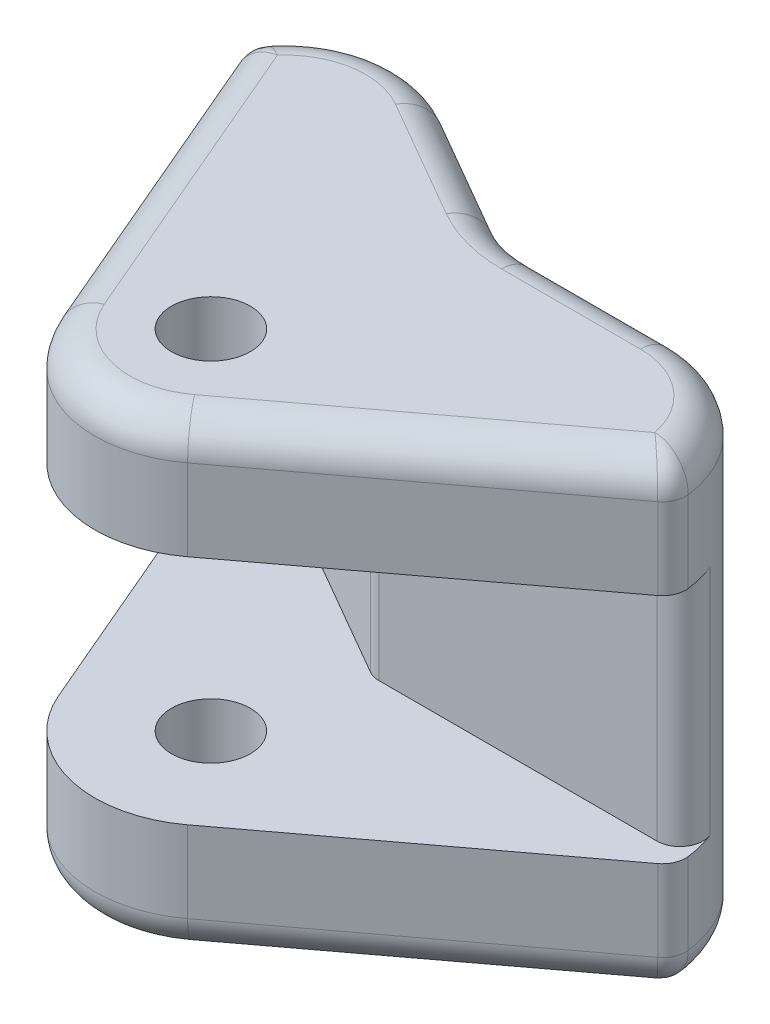
SolidWorks part; units mm, degrees
ref_plane "Front Plane" through (0, 0, 0) normal (0, 0, 1) x (1, 0, 0)
ref_plane "Top Plane" through (0, 0, 0) normal (0, 1, 0) x (1, 0, 0)
ref_plane "Right Plane" through (0, 0, 0) normal (1, 0, 0) x (0, 0, -1)
sketch "Sketch1" plane through (0, 0, 0) normal (0, 1, 0) x (1, 0, 0)
  line L0 (0, 0) -> (10, 0) construction
  line L6 (0, -5) -> (10, -5)
  line L7 (0, 0) -> (-8.6603, 5) construction
  line L8 (-2.5, -4.3301) -> (-11.1603, 0.6699)
  line L10 (-12.9904, 7.5) -> (-10.4904, 11.8301)
  line L11 (15, 0) -> (15, 5)
  line L12 (-3.6603, 13.6603) -> (1.5192, 10.6699)
  line L13 (4.0192, 10) -> (10, 10)
  line L14 (0, 0) -> (0, -5) construction
  line L15 (0, 0) -> (-2.5, -4.3301) construction
  arc A8 (10, -5) -> (15, 0) centre (10, 0) ccw
  arc A10 (-12.9904, 7.5) -> (-11.1603, 0.6699) centre (-8.6603, 5) ccw
  arc A11 (1.5192, 10.6699) -> (4.0192, 10) centre (4.0192, 15) ccw
  arc A12 (-10.4904, 11.8301) -> (-3.6603, 13.6603) centre (-6.1603, 9.3301) cw
  arc A13 (15, 5) -> (10, 10) centre (10, 5) ccw
  arc A14 (-2.5, -4.3301) -> (0, -5) centre (0, 0) ccw
  circle A15 centre (0, 0) radius 1.7
  point P3 (5, 0)
  point P8 (-4.3301, 2.5)
  point P25 (-7.9904, 16.1603)
  point P28 (15, 10)
  dimension "D1" = 5.9808
  dimension "D2" = 5
  dimension "D3" = 150
  dimension "D4" = 10
  dimension "D9" = 5
  dimension "D10" = 5
  dimension "D11" = 5
  dimension "D15" = 3.4
  dimension "D5" = 10
  dimension "D6" = 10
  dimension "D7" = 10
  dimension "D8" = 150
  dimension "D12" = 5
  dimension "D13" = 8.6603
  dimension "D14" = 150
extrude "Boss-Extrude1" add sketch "Sketch1" along normal blind 5
sketch "Sketch2" plane through (0, 5, 0) normal (0, 1, 0) x (1, 0, 0)
  line L0 (0, 0) -> (-8.6603, 5) construction
  line L2 (1.3397, 5) -> (-6.1603, 9.3301)
  line L3 (0, 0) -> (10, 0) construction
  line L4 (1.3397, 5) -> (10, 5)
  line L7 (-3.6603, 13.6603) -> (1.5192, 10.6699)
  line L8 (4.0192, 10) -> (10, 10)
  line L11 (10, 10) -> (4.0192, 10) construction
  line L13 (1.5192, 10.6699) -> (-3.6603, 13.6603) construction
  line L14 (10, 5) -> (15, 5)
  line L15 (-6.1603, 9.3301) -> (-10.4904, 11.8301)
  arc A0 (1.5192, 10.6699) -> (4.0192, 10) centre (4.0192, 15) ccw
  arc A1 (-3.6603, 13.6603) -> (-10.4904, 11.8301) centre (-6.1603, 9.3301) ccw
  arc A2 (15, 5) -> (10, 10) centre (10, 5) ccw
  point P4 (-4.3301, 2.5)
  point P9 (5, 0)
  dimension "D4" = 5
  dimension "D5" = 5
  dimension "D1" = 150
  dimension "D2" = 11.8301
  dimension "D3" = 6.8301
extrude "Boss-Extrude2" add sketch "Sketch2" along normal blind 10
sketch "Sketch3" plane through (0, 15, 0) normal (0, 1, 0) x (1, 0, 0)
  line L0 (-10.4904, 11.8301) -> (-4.5981, -1.9641)
  line L1 (15, 5) -> (3, -4)
  line L2 (10, 10) -> (4.0192, 10)
  line L3 (1.5192, 10.6699) -> (-3.6603, 13.6603)
  line L4 (1.5192, 10.6699) -> (-3.6603, 13.6603) construction
  arc A0 (-4.5981, -1.9641) -> (3, -4) centre (0, 0) ccw
  arc A1 (-2.5, -4.3301) -> (0, -5) centre (0, 0) ccw construction
  arc A2 (4.0192, 10) -> (1.5192, 10.6699) centre (4.0192, 15) cw
  arc A3 (-10.4904, 11.8301) -> (-3.6603, 13.6603) centre (-6.1603, 9.3301) cw
  arc A4 (10, 10) -> (15, 5) centre (10, 5) cw
  arc A5 (15, 5) -> (10, 10) centre (10, 5) ccw construction
  arc A6 (-3.6603, 13.6603) -> (-10.4904, 11.8301) centre (-6.1603, 9.3301) ccw construction
  circle A7 centre (0, 0) radius 1.7
  dimension "D1" = 5
  dimension "D2" = 3.4
extrude "Boss-Extrude3" add sketch "Sketch3" along normal blind 5
sketch "Sketch4" plane through (0, 5, 0) normal (0, 1, 0) x (1, 0, 0)
  line L0 (-10.4904, 11.8301) -> (1.3397, 5)
  line L1 (1.3397, 5) -> (15, 5)
  line L2 (1.3397, 5) -> (15, 5) construction
  line L3 (-10.4904, 11.8301) -> (1.3397, 5) construction
  line L4 (-10.4904, 11.8301) -> (-10.2404, 12.2631)
  line L5 (-10.2404, 12.2631) -> (1.4737, 5.5)
  line L6 (1.4737, 5.5) -> (15, 5.5)
  line L7 (15, 5.5) -> (15, 5)
  point P11 (3.2079, 12.0935)
  dimension "D1" = 0.5
  dimension "D2" = 0.5
extrude "Cut-Extrude1" cut sketch "Sketch4" along normal blind 10
fillet "Fillet1" radius 1 3 edges at (1.4737, 10, -5.5) (-10.2187, 10, -12.2506) (14.9749, 10, -5.5)
fillet "Fillet2" radius 1 2 edges at (-10.4904, 17.5, -11.8301) (15, 17.5, -5)
fillet "Fillet3" radius 1.5 22 edges at (-13.4899, 0, -3.7059) (-11.7404, 0, -9.6651) (-7.4543, 0, -14.1598) (-1.0705, 0, -12.1651) (2.7251, 0, -10.1704) (7.0096, 0, -10) (13.5355, 0, -8.5355) (15, 0, -2.5) (13.5355, 0, 3.5355) (5, 0, 5) (-1.2941, 0, 4.8296) (-10.3531, 20, -11.8497) (-7.1627, 20, -14.2286) (-1.0705, 20, -12.1651) (2.7251, 20, -10.1704) (7.0096, 20, -10) (13.3173, 20, -8.741) (14.8909, 20, -5.0856) (8.7856, 20, -0.3392) (-1.2941, 20, 4.8296) (-6.8301, 0, 1.8301) (-7.439, 20, -4.6866)
sketch "Sketch5" plane through (0, 0, 0) normal (0, -1, 0) x (1, 0, 0)
  line L1 (-0.8368, 3.123) -> (-3.123, 0.8368)
  line L2 (-3.123, 0.8368) -> (-2.2862, -2.2862)
  line L3 (-2.2862, -2.2862) -> (0.8368, -3.123)
  line L4 (0.8368, -3.123) -> (3.123, -0.8368)
  line L5 (3.123, -0.8368) -> (2.2862, 2.2862)
  line L6 (2.2862, 2.2862) -> (-0.8368, 3.123)
  circle A0 centre (0, 0) radius 2.8 construction
  dimension "D1" = 5.6
  dimension "D2" = 2.2862
extrude "Cut-Extrude2" cut sketch "Sketch5" against normal blind 2.6
sketch "Sketch6" plane through (0, 0, 0) normal (0, -1, 0) x (1, 0, 0)
  line L1 (16.815, 8.7492) -> (-18.4785, 8.7492)
  line L2 (16.815, 8.7492) -> (16.815, -17.3448)
  line L3 (16.815, -17.3448) -> (-18.4785, -17.3448)
  line L4 (-18.4785, 8.7492) -> (-18.4785, -17.3448)
extrude "Cut-Extrude3" cut sketch "Sketch6" against normal blind 5
sketch "Sketch7" plane through (0, 5, 0) normal (0, -1, 0) x (1, 0, 0)
  line L0 (-3.6603, -13.6603) -> (1.5192, -10.6699)
  line L1 (4.0192, -10) -> (10, -10)
  line L2 (14.5713, -4.6785) -> (3, 4)
  line L3 (-4.5981, 1.9641) -> (-10.2799, -11.3373)
  arc A0 (-3.6603, -13.6603) -> (-10.1603, -12.3301) centre (-6.1603, -9.3301) cw
  arc A1 (-10.2799, -11.3373) -> (-10.1603, -12.3301) centre (-9.3603, -11.7301) ccw
  arc A2 (10, -10) -> (14.9641, -5.5981) centre (10, -5) ccw
  arc A3 (14.5713, -4.6785) -> (14.9641, -5.5981) centre (13.9713, -5.4785) cw
  arc A4 (-4.5981, 1.9641) -> (3, 4) centre (0, 0) cw
  arc A5 (1.5192, -10.6699) -> (4.0192, -10) centre (4.0192, -15) cw
  circle A6 centre (0, 0) radius 1.7
extrude "Boss-Extrude4" add sketch "Sketch7" along normal blind 5
sketch "Sketch8" plane through (0, 0, 0) normal (0, -1, 0) x (1, 0, 0)
  line L1 (-0.8368, 3.123) -> (-3.123, 0.8368)
  line L2 (-3.123, 0.8368) -> (-2.2862, -2.2862)
  line L3 (-2.2862, -2.2862) -> (0.8368, -3.123)
  line L4 (0.8368, -3.123) -> (3.123, -0.8368)
  line L5 (3.123, -0.8368) -> (2.2862, 2.2862)
  line L6 (2.2862, 2.2862) -> (-0.8368, 3.123)
  circle A0 centre (0, 0) radius 2.8 construction
  dimension "D1" = 5.6
  dimension "D2" = 2.2862
extrude "Cut-Extrude4" cut sketch "Sketch8" against normal blind 2.6
fillet "Fillet4" radius 1.5 10 edges at (-1.2941, 0, 4.8296) (8.7856, 0, -0.3392) (14.8909, 0, -5.0856) (13.3173, 0, -8.741) (7.0096, 0, -10) (2.7251, 0, -10.1704) (-1.0705, 0, -12.1651) (-7.1627, 0, -14.2286) (-10.3531, 0, -11.8497) (-7.439, 0, -4.6866)
